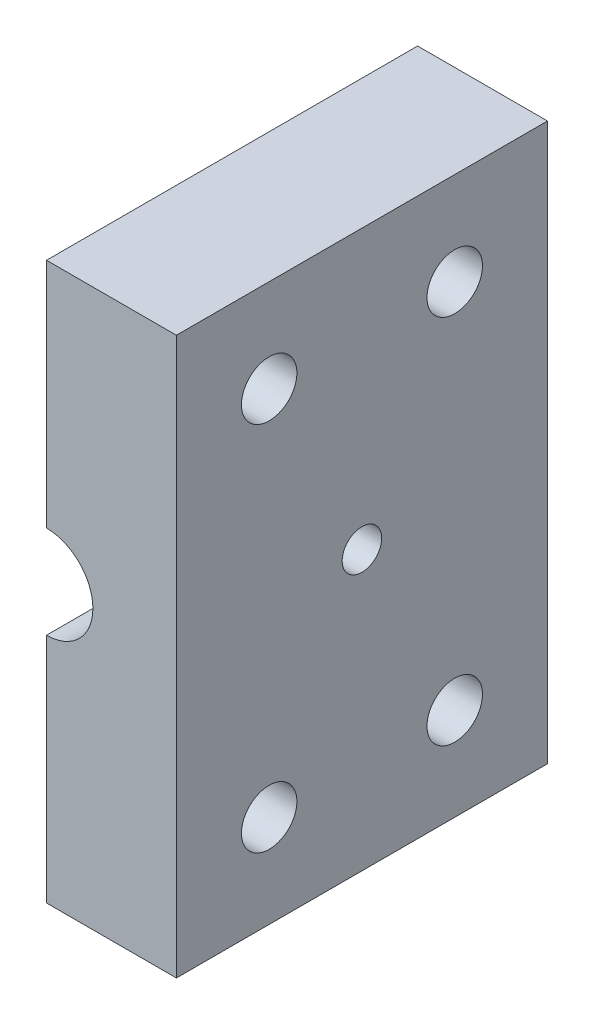
SolidWorks part; units mm, degrees
ref_plane "Front Plane" through (0, 0, 0) normal (0, 0, 1) x (1, 0, 0)
ref_plane "Top Plane" through (0, 0, 0) normal (0, 1, 0) x (1, 0, 0)
ref_plane "Right Plane" through (0, 0, 0) normal (1, 0, 0) x (0, 0, -1)
sketch "Sketch1" plane through (0, 0, 0) normal (0, 0, 1) x (1, 0, 0)
  line L1 (-4.445, -12.7) -> (4.445, -12.7)
  line L2 (-4.445, -12.7) -> (-4.445, 12.7)
  line L3 (-4.445, 12.7) -> (4.445, 12.7)
  line L4 (4.445, -12.7) -> (4.445, 12.7)
  line L5 (-4.445, -12.7) -> (4.445, 12.7) construction
  line L6 (-4.445, 12.7) -> (4.445, -12.7) construction
  point P0 (0, 0)
  dimension "D1" = 25.4
  dimension "D2" = 8.89
extrude "Boss-Extrude1" add sketch "Sketch1" along normal mid plane 25.4
sketch "Sketch2" plane through (0, 0, 12.7) normal (0, 0, 1) x (1, 0, 0)
  line L0 (-4.445, -12.7) -> (4.445, -12.7) construction
  line L1 (-4.445, 12.7) -> (-4.445, -12.7) construction
  circle A0 centre (-4.445, -6.35) radius 3.175
  dimension "D2" = 6.35
  dimension "D1" = 6.35
extrude "Cut-Extrude1" cut sketch "Sketch2" against normal blind 25.4
sketch "Sketch3" plane through (4.445, 0, 0) normal (1, 0, 0) x (0, 0, -1)
  line L0 (-6.35, 6.35) -> (6.35, 6.35) construction
  line L1 (0, 4.8895) -> (0, -4.8895) construction
  line L2 (-12.7, 12.7) -> (12.7, 12.7) construction
  point P0 (-6.35, 6.35)
  point P1 (6.35, 6.35)
  point P4 (0, 6.35)
  dimension "D1" = 12.7
  dimension "D2" = 6.35
hole_wizard "#6 Clearance Hole2" positions "Sketch4" profile "Sketch6" hole size "#6" standard "ANSI Inch" end condition through all
sketch "Sketch4" plane through (4.445, 0, 0) normal (1, 0, 0) x (0, 0, -1)
  point P0 (-6.35, 6.35)
  point P3 (6.35, 6.35)
sketch "Sketch6" plane through (4.445, 6.35, 6.35) normal (0, 1, 0) x (0, 0, -1)
  line L0 (0, 0) -> (0, 8.89)
  line L1 (0, 8.89) -> (1.8986, 8.89)
  line L2 (1.8986, 8.89) -> (1.8986, 0)
  line L5 (1.8986, 0) -> (0, 0)
  line L11 (0, -6.35) -> (0, 107.95) construction
  dimension "Thru Hole Dia." = 3.7973
  dimension "Thru Hole Depth" = 8.89
sketch "Sketch7" plane through (4.445, 0, 0) normal (1, 0, 0) x (0, 0, -1)
  line L0 (-12.7, -12.7) -> (12.7, -12.7) construction
  line L1 (0, 4.8895) -> (0, -4.8895) construction
  point P0 (0, -6.35)
  dimension "D1" = 6.35
hole_wizard "#6-32 Tapped Hole1" positions "Sketch8" profile "Sketch9" tap size "#6-32" standard "ANSI Inch" end condition through all
sketch "Sketch8" plane through (4.445, 0, 0) normal (1, 0, 0) x (0, 0, -1)
  point P0 (0, -6.35)
sketch "Sketch9" plane through (4.445, -6.35, 0) normal (0, 1, 0) x (0, 0, -1)
  line L0 (0, 0) -> (0, 8.89)
  line L1 (0, 8.89) -> (1.3525, 8.89)
  line L2 (1.3525, 8.89) -> (1.3525, 0)
  line L5 (1.3525, 0) -> (0, 0)
  line L11 (0, -6.35) -> (0, 107.95) construction
  dimension "Thread Major Dia." = 2.7051
  dimension "Thru Tap Drill Depth" = 8.89
ref_point "Point1"
ref_plane "Plane1" through (0, -6.3499, 0) normal (0, 1, 0) x (1, 0, 0)
mirror "Mirror1" about plane through (0, -6.3499, 0) normal (0, 1, 0) of "#6-32 Tapped Hole1", "#6 Clearance Hole2", "Cut-Extrude1", "Boss-Extrude1"
